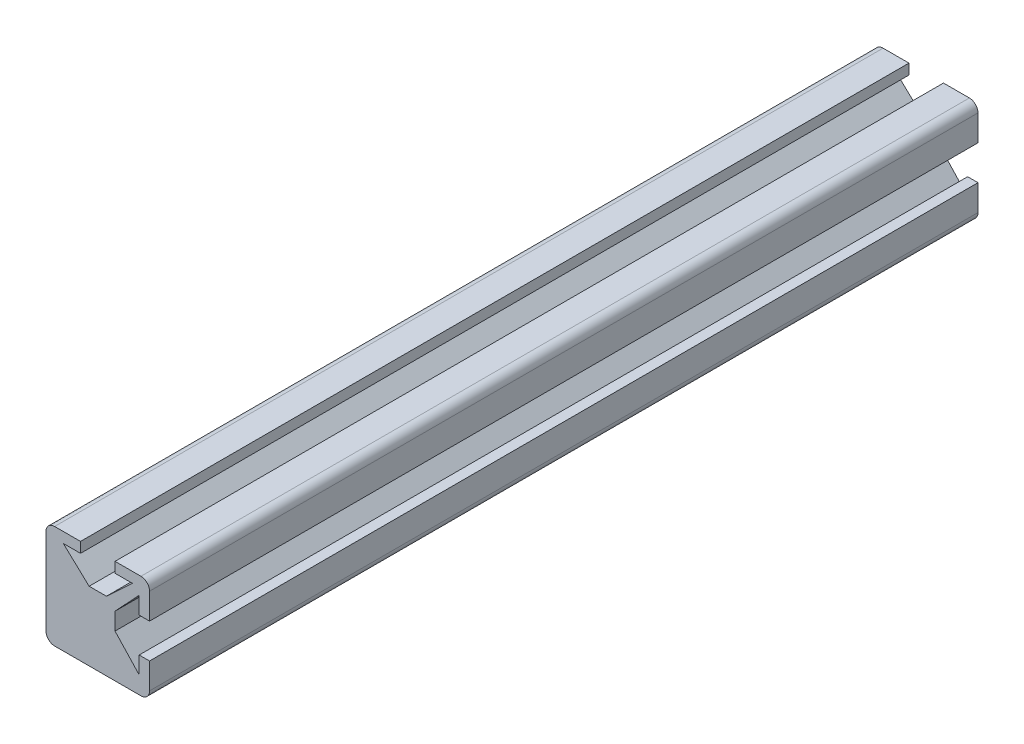
SolidWorks part; units mm, degrees
ref_plane "Plan de face" through (0, 0, 0) normal (0, 0, 1) x (1, 0, 0)
ref_plane "Plan de dessus" through (0, 0, 0) normal (0, 1, 0) x (1, 0, 0)
ref_plane "Plan de droite" through (0, 0, 0) normal (1, 0, 0) x (0, 0, -1)
sketch "Esquisse1" plane through (0, 0, 0) normal (0, 0, 1) x (1, 0, 0)
  line L0 (-6, 5) -> (-6, -5)
  line L1 (-5, 6) -> (5, 6)
  line L2 (-5, -6) -> (5, -6)
  line L3 (6, 5) -> (6, -5)
  line L4 (-5, 5) -> (5, -5) construction
  line L5 (5, 5) -> (-5, -5) construction
  arc A0 (-5, 6) -> (-6, 5) centre (-5, 5) ccw
  arc A1 (5, 6) -> (6, 5) centre (5, 5) cw
  arc A2 (6, -5) -> (5, -6) centre (5, -5) cw
  arc A3 (-5, -6) -> (-6, -5) centre (-5, -5) cw
  point P12 (0, 0)
  dimension "D1" = 1
  dimension "D2" = 1
  dimension "D4" = 1
  dimension "D3" = 12
extrude "Extrusion1" add sketch "Esquisse1" along normal mid plane 96
sketch "Esquisse3" plane through (0, 0, 48) normal (0, 0, 1) x (1, 0, 0)
  line L0 (6, 2) -> (4.8, 2)
  line L2 (4.8, 2) -> (4.8, 4)
  line L3 (2, 1) -> (2, -1)
  line L4 (4.8, -4) -> (4.8, -2)
  line L5 (4.8, -2) -> (6, -2)
  line L6 (6, -5) -> (6, 5) construction
  line L7 (4.8, 4) -> (2, 1)
  line L8 (6, 2) -> (6, -2)
  line L9 (4.8, -4) -> (2, -1)
  point P4 (6, 0)
  point P10 (6, 0)
  dimension "D1" = 4
  dimension "D2" = 1.2
  dimension "D3" = 4
  dimension "D4" = 2
  dimension "D5" = 2
extrude "Enlèv. mat.-Extru.1" cut sketch "Esquisse3" against normal through all
ref_axis "Axe1" through (0, 0, -1) along (0, 0, 1)
pattern_circular "Répétition circulaire1" count 2 every 90 about axis through (0, 0, -1) along (0, 0, 1) of "Enlèv. mat.-Extru.1"
